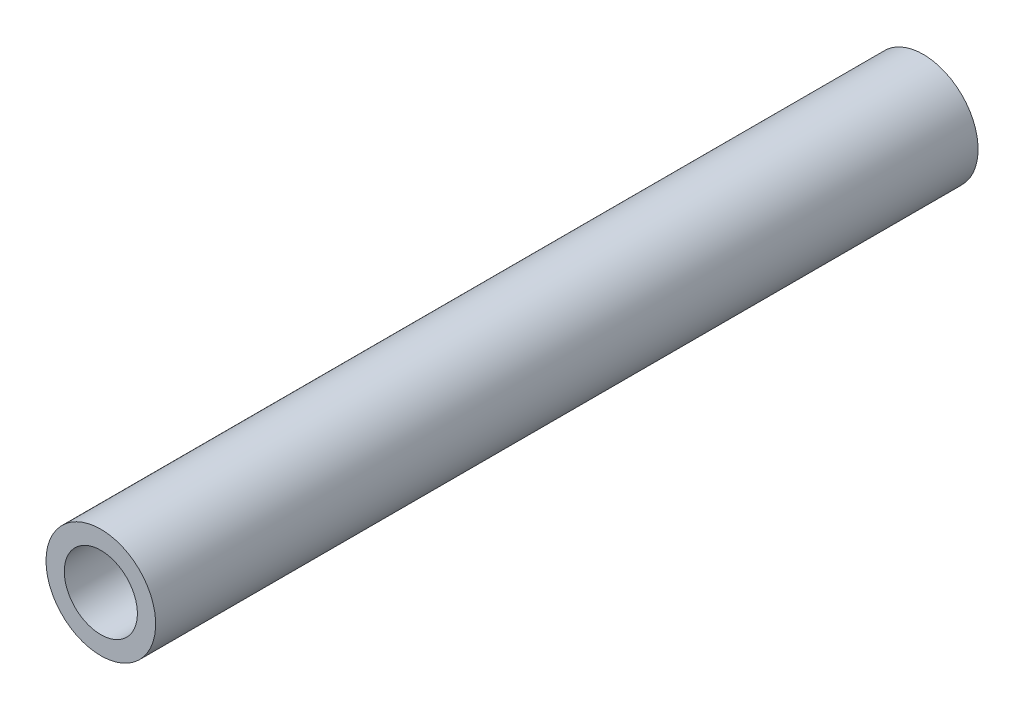
SolidWorks part; units mm, degrees
material "C-Fibra di vetro"
ref_plane "Piano frontale" through (0, 0, 0) normal (0, 0, 1) x (1, 0, 0)
ref_plane "Piano superiore" through (0, 0, 0) normal (0, 1, 0) x (1, 0, 0)
ref_plane "Piano destro" through (0, 0, 0) normal (1, 0, 0) x (0, 0, -1)
sketch "Schizzo1" plane through (0, 0, 0) normal (0, 0, 1) x (1, 0, 0)
  circle A0 centre (70, -80.5) radius 3
  circle A1 centre (70, -80.5) radius 2
  dimension "D1" = 6
  dimension "D2" = 1
extrude "Estrusione-Estrusione1" add sketch "Schizzo1" along normal up to surface (45 mm away)
